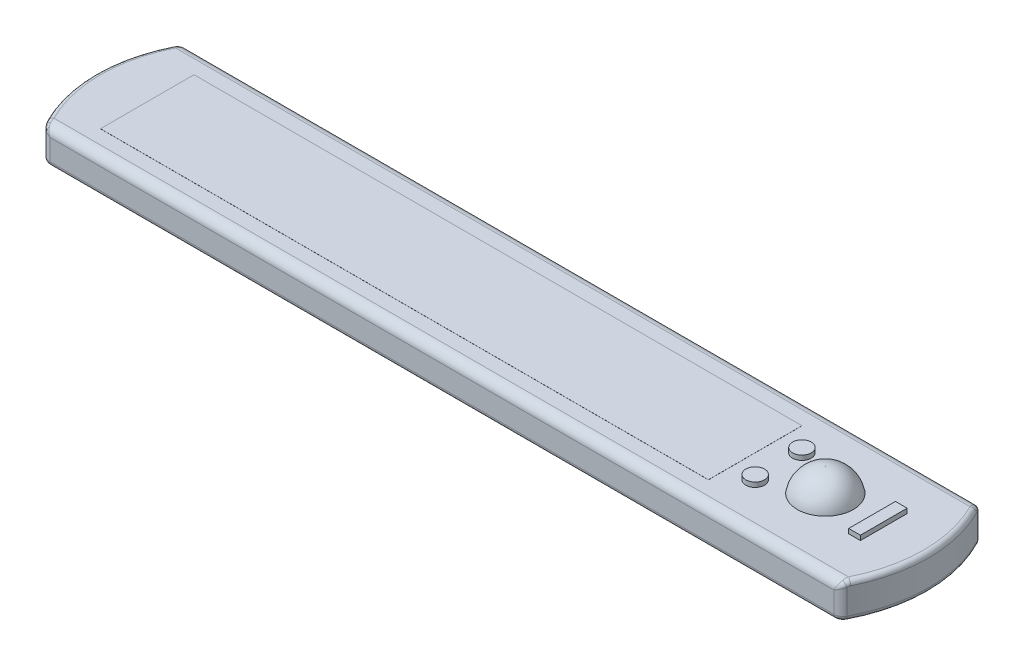
SolidWorks part; units mm, degrees
ref_plane "Front Plane" through (0, 0, 0) normal (0, 0, 1) x (1, 0, 0)
ref_plane "Top Plane" through (0, 0, 0) normal (0, 1, 0) x (1, 0, 0)
ref_plane "Right Plane" through (0, 0, 0) normal (1, 0, 0) x (0, 0, -1)
sketch "Sketch1" plane through (0, 0, 0) normal (0, 1, 0) x (1, 0, 0)
  line L3 (0, 19.05) -> (215.9, 19.05)
  line L4 (215.9, -19.05) -> (0, -19.05)
  line L5 (0, 19.05) -> (0, -19.05) construction
  line L8 (215.9, 19.05) -> (215.9, -19.05) construction
  arc A2 (0, 19.05) -> (0, -19.05) centre (32.9956, 0) ccw
  arc A3 (215.9, 19.05) -> (215.9, -19.05) centre (182.9044, 0) cw
  point P0 (0, 0)
  dimension "D1" = 38.1
  dimension "D3" = 38.1
  dimension "D2" = 215.9
extrude "Boss-Extrude1" add sketch "Sketch1" along normal blind 9.525
fillet "Fillet1" radius 2.54 6 edges at (107.95, 9.525, -19.05) (107.95, 9.525, 19.05) (0, 4.7625, 19.05) (0, 4.7625, -19.05) (215.9, 4.7625, -19.05) (215.9, 4.7625, 19.05)
fillet "Fillet2" radius 1.27 18 edges at (107.95, 0, 19.05) (221.0044, 0, 0) (107.95, 0, -19.05) (-5.1044, 0, 0) (216.7806, 9.3502, 17.4361) (217.1071, 9.5099, -16.7866) (-0.8806, 9.3502, -17.4361) (-1.2071, 9.5099, 16.7866) (221.0044, 9.525, 0) (-5.1044, 9.525, 0) (0.186, 0, -18.6834) (0.186, 0, 18.6834) (215.714, 0, 18.6834) (215.714, 0, -18.6834) (215.714, 8.2996, 18.6834) (215.714, 8.2996, -18.6834) (0.186, 8.2996, -18.6834) (0.186, 8.2996, 18.6834)
sketch "Sketch2" plane through (0, 9.525, 0) normal (0, 1, 0) x (1, 0, 0)
  line L0 (180.34, 6.35) -> (180.34, -6.35) construction
  line L1 (8.89, 12.7) -> (173.99, 12.7)
  line L2 (8.89, 12.7) -> (8.89, -12.7)
  line L3 (8.89, -12.7) -> (173.99, -12.7)
  line L4 (173.99, 12.7) -> (173.99, -12.7)
  line L5 (205.74, 6.35) -> (208.915, 6.35)
  line L6 (205.74, 6.35) -> (205.74, -6.35)
  line L7 (205.74, -6.35) -> (208.915, -6.35)
  line L8 (208.915, 6.35) -> (208.915, -6.35)
  circle A0 centre (193.04, 0) radius 7.62
  circle A1 centre (180.34, 6.35) radius 2.54
  circle A2 centre (180.34, -6.35) radius 2.54
  point P4 (8.89, 0)
  point P12 (208.915, 0)
  point P17 (180.34, 0)
  dimension "D4" = 12.7
  dimension "D6" = 15.24
  dimension "D9" = 5.08
  dimension "D1" = 25.4
  dimension "D2" = 165.1
  dimension "D3" = 8.89
  dimension "D5" = 3.175
  dimension "D7" = 19.05
  dimension "D8" = 12.7
  dimension "D10" = 12.7
  dimension "D11" = 6.35
extrude "Boss-Extrude2" add sketch "Sketch2" along normal blind 0.0254 contours L4 L1 L2 L3 region at (91.44, 9.525, 0)
extrude "Boss-Extrude3" add sketch "Sketch2<3>" along normal blind 6.35 contours A0 region at (193.04, 9.525, 0)
sketch "Sketch2<3>" plane through (0, 9.525, 0) normal (0, 1, 0) x (1, 0, 0) same geometry as "Sketch2"
extrude "Boss-Extrude4" add sketch "Sketch2<4>" along normal blind 1.27 contours A1 | A2 | L5 L8 L7 L6 region at (180.34, 9.525, -6.35) region at (180.34, 9.525, 6.35)
sketch "Sketch2<4>" plane through (0, 9.525, 0) normal (0, 1, 0) x (1, 0, 0) same geometry as "Sketch2"
fillet "Fillet3" radius 7.62 1 edges at (193.04, 15.875, 7.62)
ref_plane "Plane1" through (91.44, 0, 0) normal (-1, 0, 0) x (0, 0, 1)
